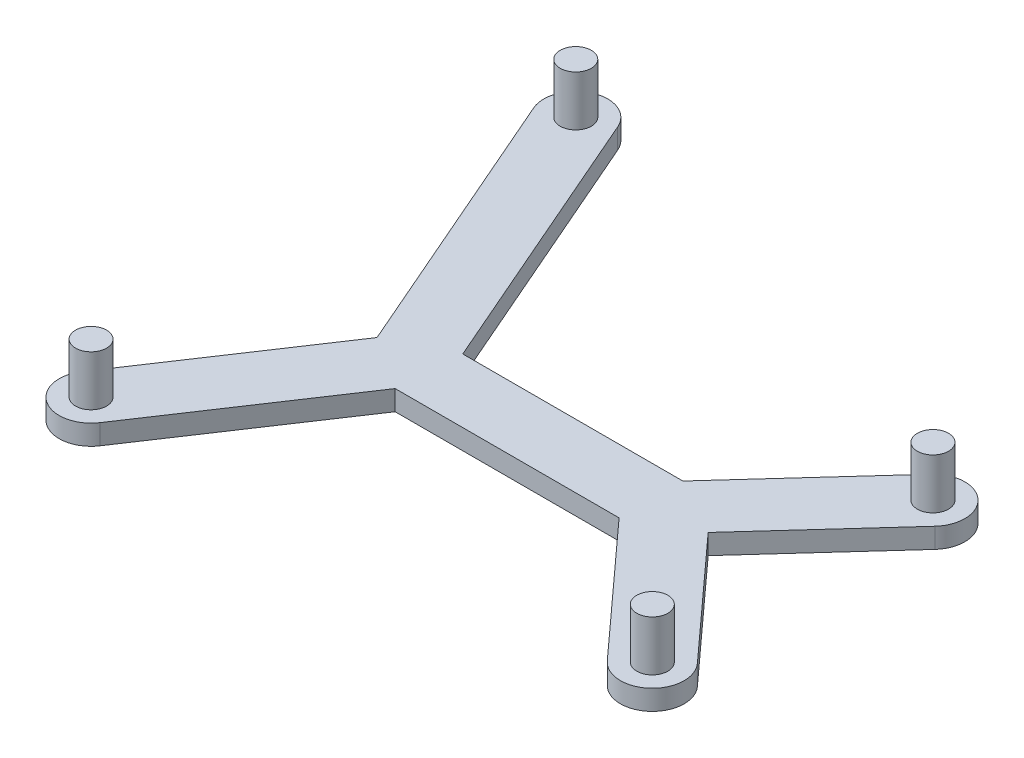
SolidWorks part; units mm, degrees
ref_plane "Front Plane" through (0, 0, 0) normal (0, 0, 1) x (1, 0, 0)
ref_plane "Top Plane" through (0, 0, 0) normal (0, 1, 0) x (1, 0, 0)
ref_plane "Right Plane" through (0, 0, 0) normal (1, 0, 0) x (0, 0, -1)
sketch "Sketch1" plane through (0, 0, 0) normal (0, 1, 0) x (1, 0, 0)
  line L0 (15.24, -2.54) -> (27.94, -31.75) construction
  line L1 (27.94, -31.75) -> (15.24, -50.8) construction
  line L2 (27.94, -31.75) -> (53.34, -31.75) construction
  line L3 (53.34, -31.75) -> (66.04, -17.78) construction
  line L4 (53.34, -31.75) -> (66.04, -45.72) construction
  line L5 (12.3283, -3.806) -> (24.3382, -31.4288)
  line L6 (24.3382, -31.4288) -> (12.5982, -49.0388)
  line L7 (29.6392, -34.925) -> (51.9355, -34.925)
  line L8 (57.6309, -31.75) -> (68.3893, -19.9157)
  line L9 (51.9355, -34.925) -> (63.6907, -47.8557)
  line L10 (18.1517, -1.274) -> (30.0217, -28.575)
  line L11 (29.6392, -34.925) -> (17.8818, -52.5612)
  line L12 (30.0217, -28.575) -> (51.9355, -28.575)
  line L13 (51.9355, -28.575) -> (63.6907, -15.6443)
  line L14 (57.6309, -31.75) -> (68.3893, -43.5843)
  line L15 (25.2982, -29.9888) -> (12.5982, -49.0388) construction
  line L16 (12.3283, -3.806) -> (25.0283, -33.016) construction
  line L17 (27.94, -28.575) -> (53.34, -28.575) construction
  line L18 (18.1517, -1.274) -> (30.8517, -30.484) construction
  line L19 (30.5818, -33.5112) -> (17.8818, -52.5612) construction
  line L20 (27.94, -34.925) -> (53.34, -34.925) construction
  line L21 (50.9907, -29.6143) -> (63.6907, -15.6443) construction
  line L22 (55.6893, -29.6143) -> (68.3893, -43.5843) construction
  line L23 (50.9907, -33.8857) -> (63.6907, -47.8557) construction
  line L24 (55.6893, -33.8857) -> (68.3893, -19.9157) construction
  circle A0 centre (15.24, -50.8) radius 1.55
  circle A1 centre (15.24, -2.54) radius 1.55
  circle A2 centre (66.04, -17.78) radius 1.55
  circle A3 centre (66.04, -45.72) radius 1.55
  arc A4 (12.3283, -3.806) -> (18.1517, -1.274) centre (15.24, -2.54) cw
  arc A7 (12.5982, -49.0388) -> (17.8818, -52.5612) centre (15.24, -50.8) ccw
  arc A11 (68.3893, -19.9157) -> (63.6907, -15.6443) centre (66.04, -17.78) ccw
  arc A13 (63.6907, -47.8557) -> (68.3893, -43.5843) centre (66.04, -45.72) ccw
  point P31 (26.7574, -31.75)
  point P32 (52.6731, -31.75)
  point P33 (31.5105, -26.67)
  dimension "D7" = 3.1
  dimension "D1" = 15.24
  dimension "D2" = 66.04
  dimension "D3" = 2.54
  dimension "D4" = 50.8
  dimension "D5" = 17.78
  dimension "D6" = 45.72
  dimension "D10" = 13.97
  dimension "D11" = 12.7
  dimension "D12" = 12.7
  dimension "D8" = 3.175
  dimension "D9" = 3.175
extrude "Boss-Extrude1" add sketch "Sketch1" along normal blind 5 contours A0 | A3 | A2 | A1 region at (15.24, 0, 50.8) region at (66.04, 0, 17.78) region at (66.04, 0, 45.72)
extrude "Boss-Extrude2" add sketch "Sketch1<3>" against normal blind 2 separate body contours A1 | A0 | L9 A13 L14 L8 A11 L13 L12 L10 A4 L5 L6 A7 L11 L7 A0 A1 A2 A3 | A3 | A2 region at (37.8688, 0, 29.5358) region at (15.24, 0, 50.8) region at (15.24, 0, 2.54) region at (66.04, 0, 45.72)
sketch "Sketch1<3>" plane through (0, 0, 0) normal (0, 1, 0) x (1, 0, 0) same geometry as "Sketch1"
